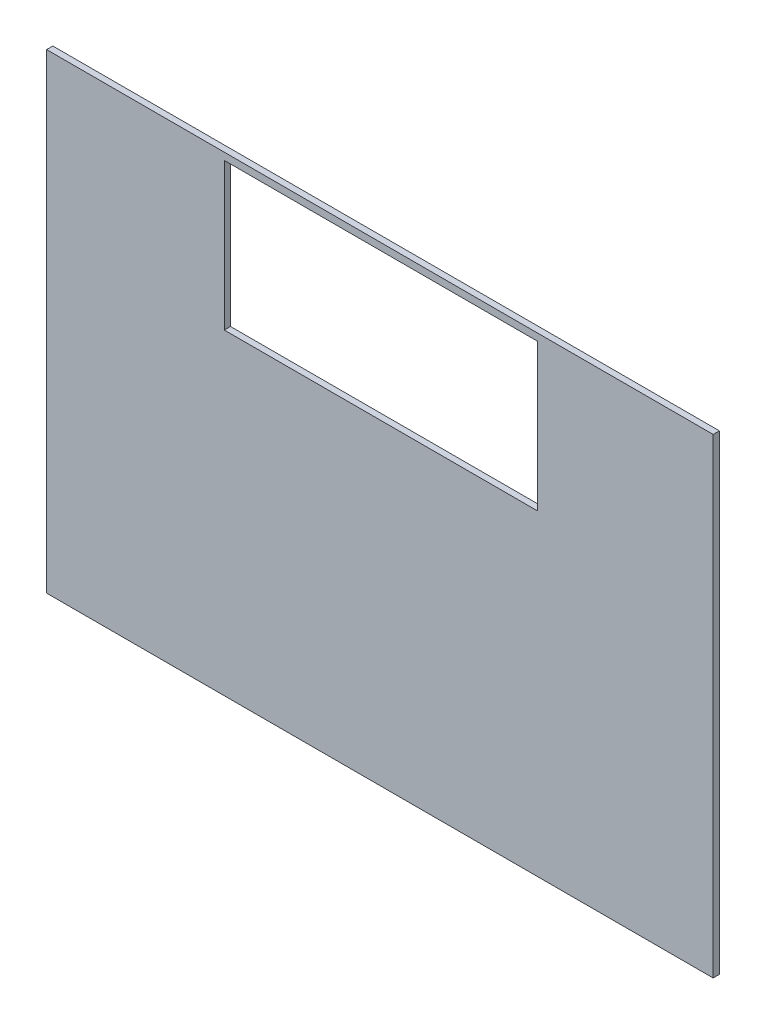
SolidWorks part; units mm, degrees
ref_plane "Front Plane" through (0, 0, 0) normal (0, 0, 1) x (1, 0, 0)
ref_plane "Top Plane" through (0, 0, 0) normal (0, 1, 0) x (1, 0, 0)
ref_plane "Right Plane" through (0, 0, 0) normal (1, 0, 0) x (0, 0, -1)
sketch "Sketch1" plane through (0, 0, 0) normal (0, 0, 1) x (1, 0, 0)
  line L1 (0, 0) -> (681.08, 0)
  line L2 (0, 0) -> (0, -481.0026)
  line L3 (0, -481.0026) -> (681.08, -481.0026)
  line L4 (681.08, 0) -> (681.08, -481.0026)
  dimension "D1" = 681.08
  dimension "D2" = 481.0026
extrude "Boss-Extrude1" add sketch "Sketch1" along normal blind 6.35
sketch "Sketch2" plane through (0, 0, 0) normal (0, 0, -1) x (-1, 0, 0)
  line L0 (-181.5418, -461.0026) -> (-181.5418, -13.0026) construction
  line L1 (-501.3881, -157.4089) -> (-181.5418, -157.4089)
  line L2 (-501.3881, -157.4089) -> (-501.3881, -7.2954)
  line L3 (-501.3881, -7.2954) -> (-181.5418, -7.2954)
  line L4 (-181.5418, -157.4089) -> (-181.5418, -7.2954)
  line L6 (-181.5418, -157.4089) -> (-501.7218, -157.4089) construction
  line L7 (-501.3881, -461.0026) -> (-501.3881, -13.0026) construction
extrude "Cut-Extrude1" cut sketch "Sketch2" against normal blind 10
